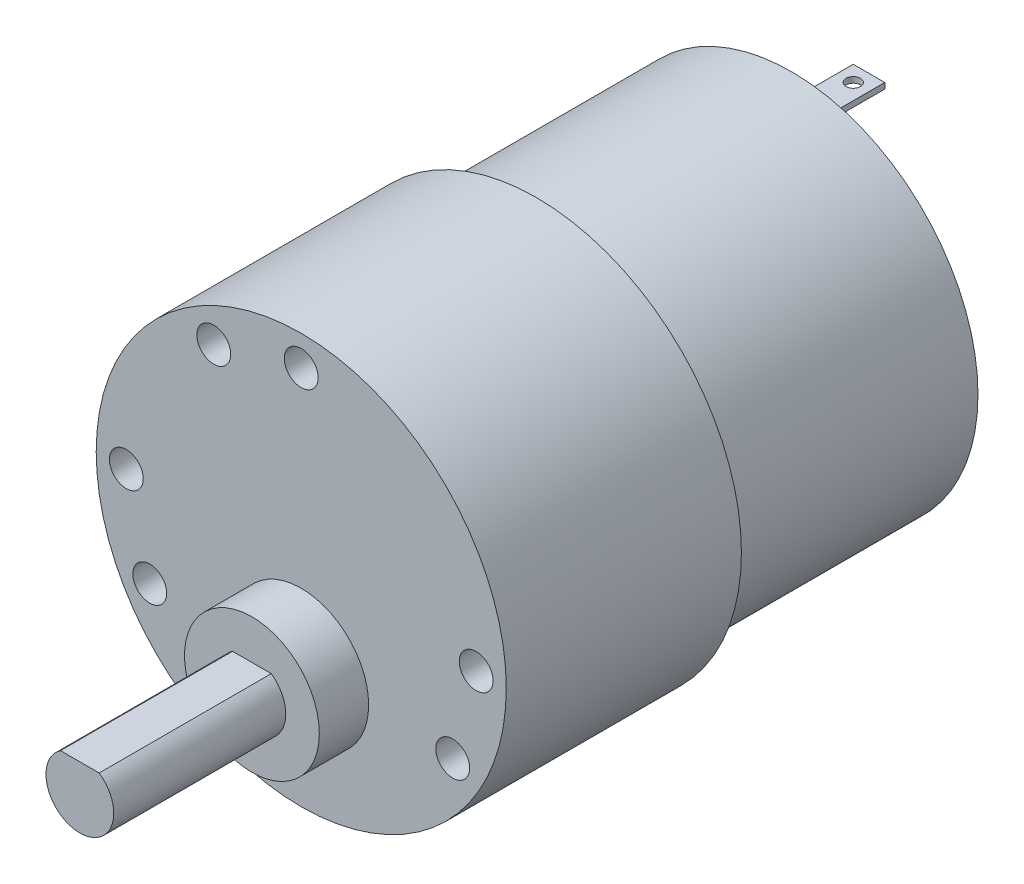
SolidWorks part; units mm, degrees
ref_plane "Front Plane" through (0, 0, 0) normal (0, 0, 1) x (1, 0, 0)
ref_plane "Top Plane" through (0, 0, 0) normal (0, 1, 0) x (1, 0, 0)
ref_plane "Right Plane" through (0, 0, 0) normal (1, 0, 0) x (0, 0, -1)
sketch "Sketch1" plane through (0, 0, 0) normal (0, 0, 1) x (1, 0, 0)
  circle A0 centre (0, 0) radius 18.161
  dimension "D1" = 36.322
extrude "Boss-Extrude1" add sketch "Sketch1" along normal blind 20.828
sketch "Sketch2" plane through (0, 0, 0) normal (0, 0, -1) x (-1, 0, 0)
  circle A0 centre (0, 0) radius 16.51
  dimension "D1" = 33.02
extrude "Boss-Extrude2" add sketch "Sketch2" along normal blind 22.606
sketch "Sketch3" plane through (0, 0, -22.606) normal (0, 0, -1) x (-1, 0, 0)
  circle A0 centre (0, 0) radius 4.5085
  dimension "D1" = 9.017
extrude "Boss-Extrude3" add sketch "Sketch3" along normal blind 3.302
sketch "Sketch4" plane through (0, 0, -22.606) normal (0, 0, -1) x (-1, 0, 0)
  circle A0 centre (0, -12.7) radius 2.413
  circle A1 centre (0, 12.7) radius 2.413
  circle A2 centre (0, 0) radius 18.161 construction
  dimension "D1" = 4.826
  dimension "D2" = 4.826
  dimension "D3" = 12.7
  dimension "D4" = 12.7
extrude "Boss-Extrude4" add sketch "Sketch4" along normal blind 1.27
sketch "Sketch5" plane through (0, 0, 20.828) normal (0, 0, 1) x (1, 0, 0)
  circle A0 centre (0, -7.366) radius 5.969
  dimension "D1" = 11.938
  dimension "D2" = 7.366
extrude "Boss-Extrude5" add sketch "Sketch5" along normal blind 4.3688
sketch "Sketch6" plane through (0, 0, 25.1968) normal (0, 0, 1) x (1, 0, 0)
  line L0 (-1.7157, -4.905) -> (1.7157, -4.905)
  arc A0 (-1.7157, -4.905) -> (1.7157, -4.905) centre (0, -7.366) ccw
  dimension "D1" = 6
  dimension "D2" = 2.461
extrude "Boss-Extrude6" add sketch "Sketch6" along normal blind 15.24
ref_axis "Axis2" through (0, 12.7, -23.876) along (0, 0, 1)
ref_axis "Axis3" through (0, -12.7, -23.876) along (0, 0, 1)
ref_plane "Plane1" through (0, 0, 0) normal (1, 0, 0) x (0, 0, -1)
ref_plane "Plane2" through (0, 12.7, 0) normal (0, 1, 0) x (0, 0, 1)
ref_plane "Plane3" through (0, -12.7, 0) normal (0, 1, 0) x (0, 0, 1)
sketch "Sketch8" plane through (0, 12.7, 0) normal (0, 1, 0) x (0, 0, 1)
  line L0 (-23.876, 2.413) -> (-23.876, -2.413) construction
  line L1 (-23.876, 1.397) -> (-29.464, 1.397)
  line L2 (-23.876, 1.397) -> (-23.876, -1.397)
  line L3 (-23.876, -1.397) -> (-29.464, -1.397)
  line L4 (-29.464, 1.397) -> (-29.464, -1.397)
  line L5 (0.6985, 0) -> (-0.6985, 0) construction
  circle A0 centre (-28.067, 0) radius 0.635
  dimension "D4" = 1.27
  dimension "D1" = 2.794
  dimension "D2" = 1.397
  dimension "D3" = 5.588
  dimension "D5" = 1.397
extrude "Boss-Extrude7" add sketch "Sketch8" along normal mid plane 0.508
pattern_circular "CirPattern1" count 2 over 360 about axis through (0, 0, -25.908) along (0, 0, 1) of "Boss-Extrude7"
sketch "Sketch9" plane through (0, 0, 20.828) normal (0, 0, 1) x (1, 0, 0)
  line L0 (0, 0) -> (0, 15.494) construction
  circle A0 centre (0, 0) radius 15.494 construction
  dimension "D1" = 30.988
hole_wizard "Ø3.0mm Dowel Hole1" positions "Sketch11" profile "Sketch12" hole size "Ø3.0" standard "ANSI Metric"
sketch "Sketch11" plane through (0, 0, 20.828) normal (0, 0, 1) x (1, 0, 0)
  point P0 (0, 15.494)
sketch "Sketch12" plane through (0, 15.494, 20.828) normal (1, 0, 0) x (0, -1, 0)
  line L0 (0, 0) -> (0, 11.0613)
  line L1 (0, 11.0613) -> (1.5, 10.16)
  line L2 (1.5, 10.16) -> (1.5, 0)
  line L5 (1.5, 0) -> (0, 0)
  line L10 (0, 11.0613) -> (-1.5, 10.16) construction
  line L11 (0, -6.35) -> (0, 107.95) construction
  dimension "Hole Dia." = 3
  dimension "Hole Depth" = 10.16
  dimension "Drill Angle" = 118
pattern_circular "CirPattern2" count 12 over 360 about axis through (0, 0, 20.828) along (0, 0, -1) skipping 1, 2, 5, 6, 10 of "Ø3.0mm Dowel Hole1"
